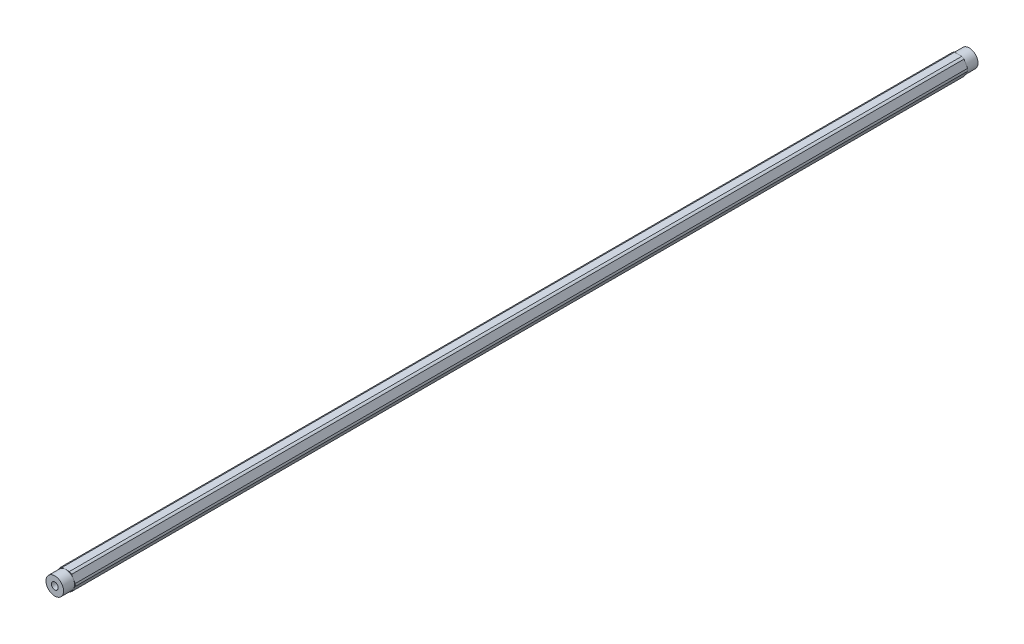
SolidWorks part; units mm, degrees
ref_plane "Front Plane" through (0, 0, 0) normal (0, 0, 1) x (1, 0, 0)
ref_plane "Top Plane" through (0, 0, 0) normal (0, 1, 0) x (1, 0, 0)
ref_plane "Right Plane" through (0, 0, 0) normal (1, 0, 0) x (0, 0, -1)
sketch "Sketch1" plane through (0, 0, 0) normal (0, 0, 1) x (1, 0, 0)
  line L1 (7.3323, 0) -> (3.6662, 6.35)
  line L2 (3.6662, 6.35) -> (-3.6662, 6.35)
  line L3 (-3.6662, 6.35) -> (-7.3323, 0)
  line L4 (-7.3323, 0) -> (-3.6662, -6.35)
  line L5 (-3.6662, -6.35) -> (3.6662, -6.35)
  line L6 (3.6662, -6.35) -> (7.3323, 0)
  circle A0 centre (0, 0) radius 6.35 construction
  dimension "D1" = 12.7
extrude "Boss-Extrude1" add sketch "Sketch1" along normal mid plane 660.4
sketch "Sketch3" plane through (0, 0, 330.2) normal (0, 0, 1) x (1, 0, 0)
  circle A0 centre (0, 0) radius 6.35
extrude "Cut-Extrude2" cut sketch "Sketch3" against normal blind 7.9502 flip side to cut
mirror "Mirror1" about plane through (0, 0, 0) normal (0, 0, 1) of "Cut-Extrude2"
sketch "Sketch4" plane through (0, 0, 330.2) normal (0, 0, 1) x (1, 0, 0)
  circle A0 centre (0, 0) radius 6.858
  dimension "D1" = 13.716
extrude "Cut-Extrude3" cut sketch "Sketch4" against normal through all flip side to cut
sketch "Sketch5" plane through (0, 0, 330.2) normal (0, 0, 1) x (1, 0, 0)
  circle A0 centre (0, 0) radius 2.4892
  dimension "D1" = 4.9784
extrude "Cut-Extrude4" cut sketch "Sketch5" against normal through all contours A0
